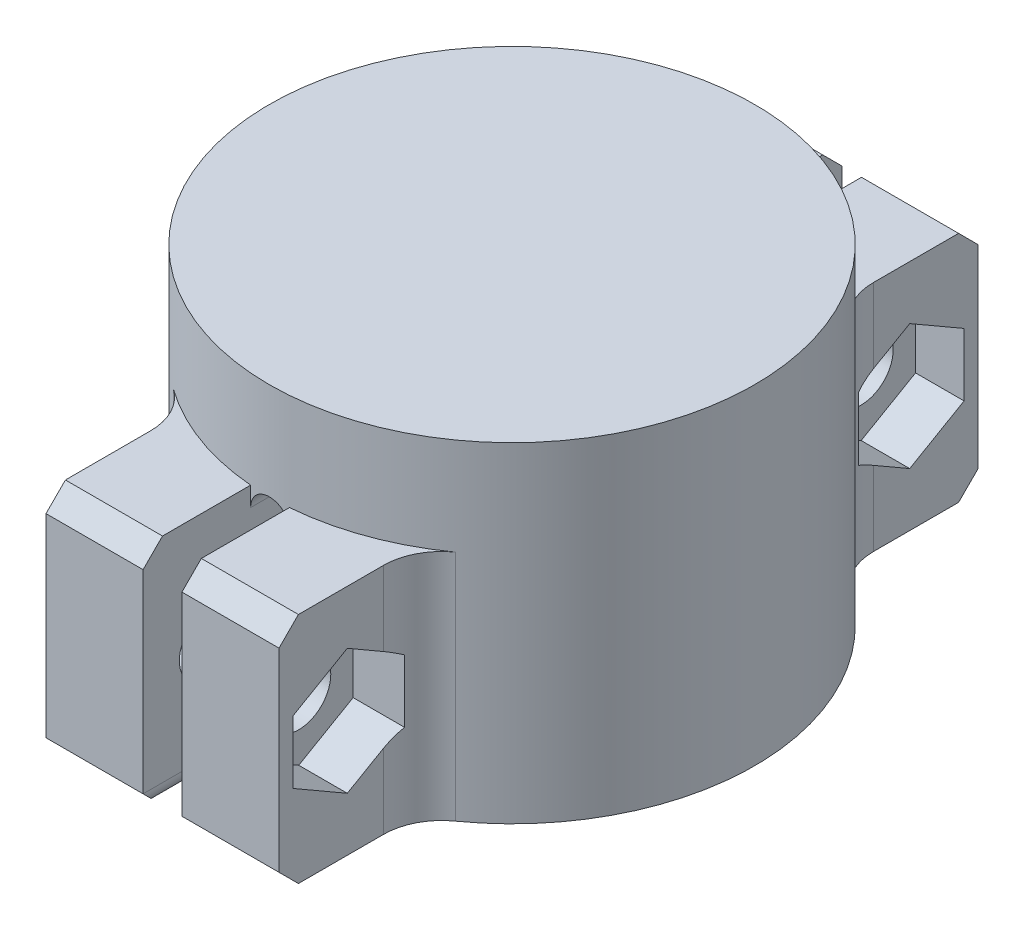
SolidWorks part; units mm, degrees
ref_plane "Front Plane" through (0, 0, 0) normal (0, 0, 1) x (1, 0, 0)
ref_plane "Top Plane" through (0, 0, 0) normal (0, 1, 0) x (1, 0, 0)
ref_plane "Right Plane" through (0, 0, 0) normal (1, 0, 0) x (0, 0, -1)
sketch "Sketch1" plane through (0, 0, 0) normal (0, 1, 0) x (1, 0, 0)
  line L0 (-6, 10.9659) -> (-6, 18)
  line L1 (-6, -18) -> (-1, -18)
  line L2 (-6, -18) -> (-6, -10.9659)
  line L3 (-6, 18) -> (-1, 18)
  line L4 (6, -18) -> (6, -10.9659)
  line L5 (-6, -18) -> (6, 18) construction
  line L6 (-6, 18) -> (6, -18) construction
  line L8 (-1, -18) -> (-1, -7.433)
  line L10 (1, -18) -> (1, -7.433)
  line L11 (-1, -18) -> (1, 18) construction
  line L12 (-1, 18) -> (1, -18) construction
  line L13 (1, 18) -> (6, 18)
  line L14 (1, -18) -> (6, -18)
  line L15 (-1, 7.433) -> (-1, 18)
  line L16 (6, 10.9659) -> (6, 18)
  line L17 (1, 7.433) -> (1, 18)
  arc A0 (-1, 7.433) -> (-1, -7.433) centre (0, 0) ccw
  arc A1 (-6, 10.9659) -> (-6, -10.9659) centre (0, 0) ccw
  circle A2 centre (0, 0) radius 12.5 construction
  arc A3 (6, -10.9659) -> (6, 10.9659) centre (0, 0) ccw
  circle A4 centre (0, 0) radius 7.5 construction
  arc A5 (1, -7.433) -> (1, 7.433) centre (0, 0) ccw
  dimension "D1" = 15
  dimension "D3" = 12
  dimension "D4" = 36
  dimension "D5" = 2
  dimension "D2" = 5
extrude "Boss-Extrude1" add sketch "Sketch1" along normal blind 12
sketch "Sketch2" plane through (0, 12, 0) normal (0, 1, 0) x (1, 0, 0)
  circle A0 centre (0, 0) radius 12.5
  point P3 (5.3202, 5.2863)
  dimension "D1" = 25
extrude "Boss-Extrude2" add sketch "Sketch2" along normal blind 5
sketch "Sketch4" plane through (-6, 0, 0) normal (-1, 0, 0) x (0, 0, 1)
  line L0 (-18, 6) -> (-10.9659, 6) construction
  line L1 (-18, 12) -> (-18, 0) construction
  line L2 (-10.9659, 12) -> (-10.9659, 0) construction
  line L3 (-10.9659, 6) -> (10.9659, 6) construction
  line L4 (10.9659, 12) -> (10.9659, 0) construction
  line L5 (10.9659, 6) -> (18, 6) construction
  line L6 (18, 12) -> (18, 0) construction
  circle A0 centre (-14.4829, 6) radius 1.65
  circle A1 centre (14.4829, 6) radius 1.65
  dimension "D1" = 3.3
  dimension "D2" = 3.3
extrude "Cut-Extrude1" cut sketch "Sketch4" against normal up to surface (12 mm away) up to face at (6, 6, 14.4829)
sketch "Sketch5" plane through (6, 0, 0) normal (1, 0, 0) x (0, 0, -1)
  line L1 (-14.4829, 9.2332) -> (-17.2829, 7.6166)
  line L2 (-17.2829, 7.6166) -> (-17.2829, 4.3834)
  line L3 (-17.2829, 4.3834) -> (-14.4829, 2.7668)
  line L4 (-14.4829, 2.7668) -> (-11.6829, 4.3834)
  line L5 (-11.6829, 4.3834) -> (-11.6829, 7.6166)
  line L6 (-11.6829, 7.6166) -> (-14.4829, 9.2332)
  line L7 (14.4829, 9.2332) -> (11.6829, 7.6166)
  line L8 (11.6829, 7.6166) -> (11.6829, 4.3834)
  line L9 (11.6829, 4.3834) -> (14.4829, 2.7668)
  line L10 (14.4829, 2.7668) -> (17.2829, 4.3834)
  line L11 (17.2829, 4.3834) -> (17.2829, 7.6166)
  line L12 (17.2829, 7.6166) -> (14.4829, 9.2332)
  circle A0 centre (-14.4829, 6) radius 2.8 construction
  circle A1 centre (14.4829, 6) radius 2.8 construction
  dimension "D1" = 5.6
  dimension "D2" = 5.6
extrude "Cut-Extrude2" cut sketch "Sketch5" against normal blind 2.5
chamfer "Chamfer1" distance 1 angle 45 8 edges at (-3.5, 12, -18) (3.5, 12, -18) (-3.5, 12, 18) (3.5, 12, 18) (3.5, 0, 18) (-3.5, 0, 18) (-3.5, 0, -18) (3.5, 0, -18)
fillet "Fillet1" radius 3 4 edges at (-6, 6, 10.9659) (-6, 6, -10.9659) (6, 6, 10.9659) (6, 6, -10.9659)
fillet "Fillet2" radius 1 4 edges at (1, 6, 7.433) (-1, 6, 7.433) (-1, 6, -7.433) (1, 6, -7.433)
fillet "Fillet3" radius 1 20 edges at (1, 12, -10.3606) (1.2141, 12, -7.643) (1, 12, 10.3606) (1.2141, 12, 7.643) (-1, 12, 10.3606) (-1.2141, 12, 7.643) (-1, 12, -10.3606) (-1.2141, 12, -7.643) (1, 0, -12.6307) (1.2141, 0, -7.643) (1, 0, 12.6307) (1.2141, 0, 7.643) (-1, 0, 12.6307) (-1.2141, 0, 7.643) (-1, 0, -12.6307) (-1.2141, 0, -7.643) (7.5, 12, 0) (-7.5, 12, 0) (7.5, 0, 0) (-7.5, 0, 0)
